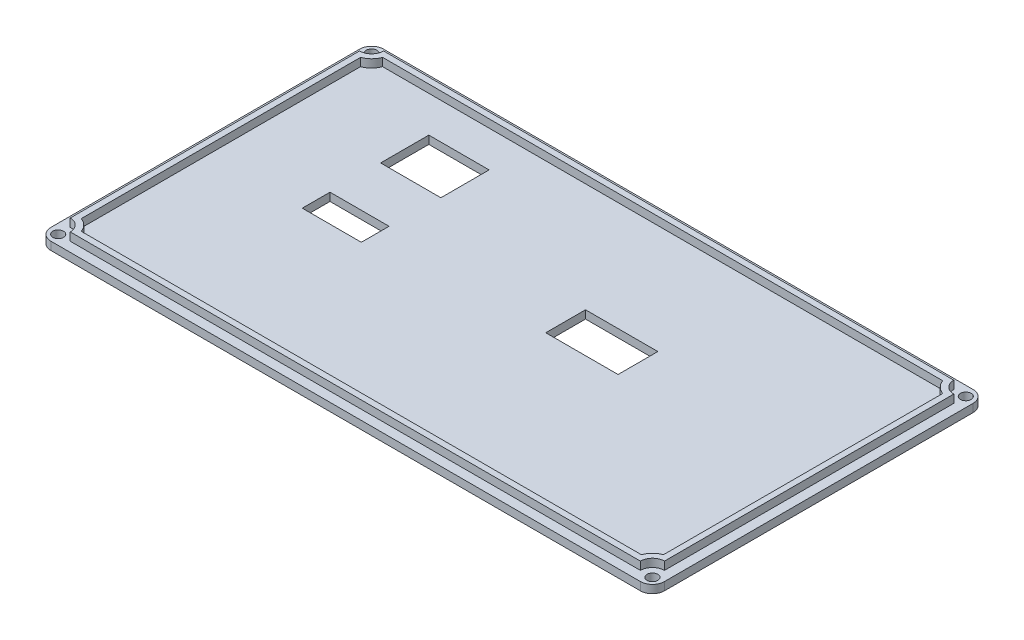
SolidWorks part; units mm, degrees
ref_plane "Front Plane" through (0, 0, 0) normal (0, 0, 1) x (1, 0, 0)
ref_plane "Top Plane" through (0, 0, 0) normal (0, 1, 0) x (1, 0, 0)
ref_plane "Right Plane" through (0, 0, 0) normal (1, 0, 0) x (0, 0, -1)
sketch "Sketch20" plane through (0, 0, 0) normal (0, 1, 0) x (1, 0, 0)
  line L0 (2.572, 21.812) -> (122.714, 21.812)
  line L1 (-2, 89.884) -> (127.286, 89.884)
  line L2 (-2, 89.884) -> (-2, 19.78)
  line L3 (-2, 19.78) -> (127.286, 19.78)
  line L4 (127.286, 89.884) -> (127.286, 19.78)
  line L5 (0.032, 85.312) -> (0.032, 24.352)
  line L10 (2.572, 87.852) -> (122.714, 87.852)
  line L11 (125.254, 85.312) -> (125.254, 24.352)
  line L15 (3.6241, 23.082) -> (121.6619, 23.082)
  line L16 (1.302, 84.2599) -> (1.302, 25.4041)
  line L17 (3.6241, 86.582) -> (121.6619, 86.582)
  line L18 (123.984, 84.2599) -> (123.984, 25.4041)
  arc A0 (0.032, 85.312) -> (2.572, 87.852) centre (0.032, 87.852) ccw
  arc A1 (0.032, 24.352) -> (2.572, 21.812) centre (0.032, 21.812) cw
  arc A2 (122.714, 87.852) -> (125.254, 85.312) centre (125.254, 87.852) ccw
  arc A3 (122.714, 21.812) -> (125.254, 24.352) centre (125.254, 21.812) cw
  arc A5 (1.302, 84.2599) -> (3.6241, 86.582) centre (0.032, 87.852) ccw
  arc A6 (1.302, 25.4041) -> (3.6241, 23.082) centre (0.032, 21.812) cw
  arc A7 (121.6619, 86.582) -> (123.984, 84.2599) centre (125.254, 87.852) ccw
  arc A8 (121.6619, 23.082) -> (123.984, 25.4041) centre (125.254, 21.812) cw
  dimension "D21" = 2.54
  dimension "D22" = 2.54
  dimension "D23" = 2.54
  dimension "D24" = 2.54
  dimension "D30" = 1.27
  dimension "D31" = 3.81
  dimension "D32" = 3.81
  dimension "D33" = 3.81
  dimension "D28" = 3.81
  dimension "D2" = 70.104
  dimension "D4" = 129.286
  dimension "D7" = 2.032
  dimension "D8" = 2.032
  dimension "D9" = 2.032
  dimension "D10" = 2.032
  dimension "D13" = 4.572
  dimension "D14" = 4.572
  dimension "D15" = 4.572
  dimension "D16" = 4.572
  dimension "D17" = 4.572
  dimension "D18" = 4.572
  dimension "D19" = 4.572
  dimension "D20" = 4.572
  dimension "D25" = 1.27
  dimension "D26" = 1.27
  dimension "D27" = 1.27
extrude "Boss-Extrude5" add sketch "Sketch20" against normal blind 1.7 separate body contours L4 L3 L2 L1
extrude "Boss-Extrude6" add sketch "Sketch20<3>" along normal blind 1.7 contours L17 A7 L18 A8 L15 A6 L16 A5 | L10 A2 L11 A3 L0 A1 L5 A0
sketch "Sketch20<3>" plane through (0, 0, 0) normal (0, 1, 0) x (1, 0, 0) same geometry as "Sketch20"
fillet "Fillet3" radius 2.54 4 edges at (-2, -0.85, -19.78) (-2, -0.85, -89.884) (127.286, -0.85, -89.884) (127.286, -0.85, -19.78)
hole_wizard "#4-40 Tapped Hole3" positions "Sketch27" profile "Sketch25" tap size "#4-40" standard "ANSI Inch" end condition through all
sketch "Sketch27" plane through (0, 0, 0) normal (0, 1, 0) x (1, 0, 0)
  point P0 (0.032, 21.812)
  point P3 (125.254, 21.812)
  point P6 (125.254, 87.852)
  point P9 (0.032, 87.852)
cosmetic thread "Hole Thread15" parameters "D2"=2.8448
cosmetic thread "Hole Thread16" parameters "D2"=2.8448
cosmetic thread "Hole Thread17" parameters "D2"=2.8448
cosmetic thread "Hole Thread18" parameters "D2"=2.8448
sketch "Sketch25" plane through (0.032, 0, -21.812) normal (1, 0, 0) x (0, 0, 1)
  line L0 (0, 0) -> (0, 1.7)
  line L1 (0, 1.7) -> (1.1303, 1.7)
  line L2 (1.1303, 1.7) -> (1.1303, 0)
  line L5 (1.1303, 0) -> (0, 0)
  line L11 (0, -6.35) -> (0, 107.95) construction
  dimension "Thru Tap Drill Dia." = 2.2606
  dimension "Thru Tap Drill Depth" = 1.7
sketch "Sketch28" plane through (0, -1.7, 0) normal (0, -1, 0) x (1, 0, 0)
  line L0 (2.572, -24.352) -> (122.714, -24.352)
  line L1 (69.374, -55.213) -> (84.614, -55.213)
  line L2 (69.374, -55.213) -> (69.374, -63.595)
  line L3 (69.374, -63.595) -> (84.614, -63.595)
  line L4 (84.614, -55.213) -> (84.614, -63.595)
  line L5 (2.572, -24.352) -> (2.572, -85.312)
  line L6 (2.572, -85.312) -> (122.714, -85.312)
  line L7 (122.714, -24.352) -> (122.714, -85.312)
  line L8 (-2, -87.344) -> (-2, -22.32) construction
  line L9 (127.286, -87.344) -> (127.286, -22.32) construction
  line L10 (0.54, -19.78) -> (124.746, -19.78) construction
  line L11 (0.54, -89.884) -> (124.746, -89.884) construction
  line L12 (12.097, -24.352) -> (12.097, -85.312) construction
  line L14 (20.987, -68.802) -> (33.687, -68.802)
  line L15 (20.987, -68.802) -> (20.987, -78.962)
  line L16 (20.987, -78.962) -> (33.687, -78.962)
  line L17 (33.687, -68.802) -> (33.687, -78.962)
  line L18 (20.987, -52.292) -> (33.433, -52.292)
  line L19 (20.987, -52.292) -> (20.987, -58.134)
  line L20 (20.987, -58.134) -> (33.433, -58.134)
  line L21 (33.433, -52.292) -> (33.433, -58.134)
  point P26 (20.987, -55.213)
  point P27 (27.21, -52.292)
  dimension "D1" = 4.572
  dimension "D2" = 4.572
  dimension "D3" = 4.572
  dimension "D4" = 4.572
  dimension "D5" = 21.717
  dimension "D6" = 38.1
  dimension "D7" = 8.382
  dimension "D8" = 15.24
  dimension "D9" = 9.525
  dimension "D10" = 8.89
  dimension "D11" = 10.16
  dimension "D12" = 6.35
  dimension "D13" = 12.7
  dimension "D14" = 5.842
  dimension "D15" = 12.446
  dimension "D16" = 18.415
  dimension "D17" = 27.94
extrude "Cut-Extrude1" cut sketch "Sketch28" against normal blind 2.54 contours L17 L14 L15 L16 | L4 L1 L2 L3 | L18 L21 L20 L19 region at (76.994, -1.7, -59.404) region at (27.337, -1.7, -73.882)
